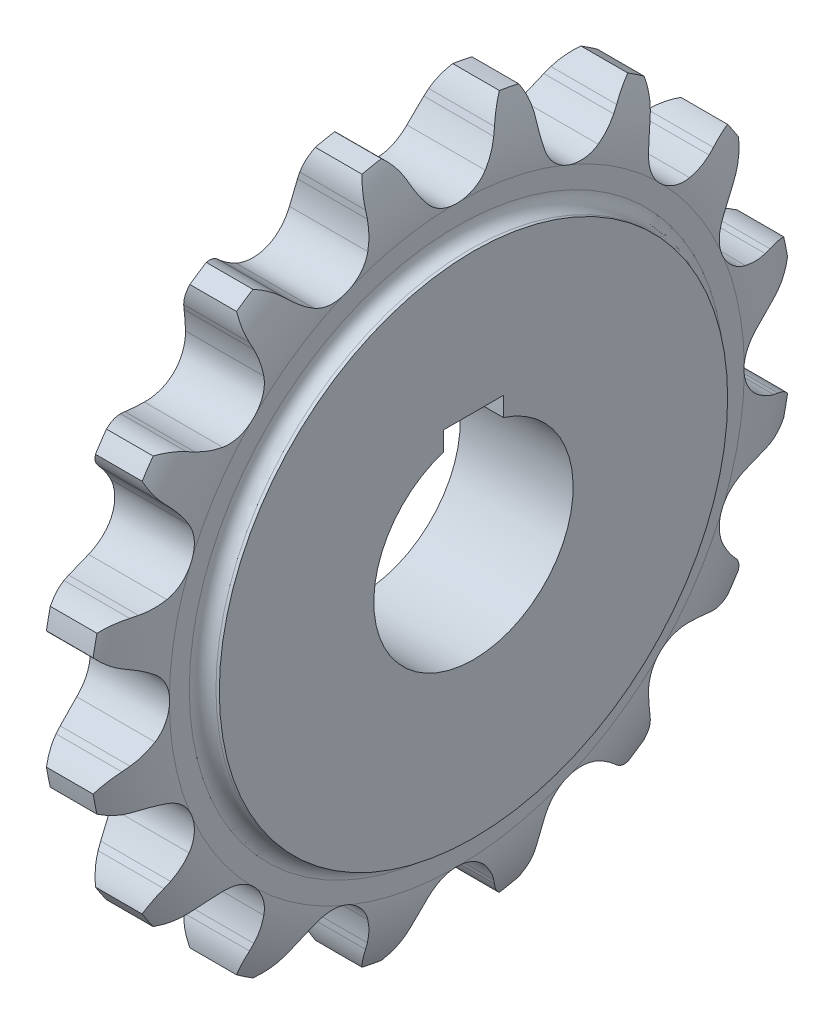
SolidWorks part; units mm, degrees
material "AISI 1020"
ref_plane "Front" through (0, 0, 0) normal (0, 0, 1) x (1, 0, 0)
ref_plane "Top" through (0, 0, 0) normal (0, 1, 0) x (1, 0, 0)
ref_plane "Right" through (0, 0, 0) normal (1, 0, 0) x (0, 0, -1)
sketch "Sketch1" plane through (0, 0, 0) normal (0, 0, 1) x (1, 0, 0)
  line L0 (-4, 0) -> (4, 0) construction
  line L1 (-16.9955, 0) -> (-16.9955, 76.5)
  line L2 (-16.9955, 76.5) -> (-15.9923, 76.5)
  line L3 (-11.9795, 80.5128) -> (-11.9795, 86.5321)
  line L4 (-7.0265, 106) -> (7.0265, 106)
  line L5 (11.9795, 86.5321) -> (11.9795, 80.5128)
  line L6 (15.9923, 76.5) -> (16.9955, 76.5)
  line L7 (16.9955, 76.5) -> (16.9955, 0)
  line L8 (16.9955, 0) -> (-16.9955, 0)
  line L9 (0, 0) -> (0, 106) construction
  line L10 (-10.5264, 97.6471) -> (10.5264, 97.6471) construction
  line L11 (-10.5264, -97.6471) -> (10.5264, -97.6471) construction
  line L13 (-11.9795, 86.5321) -> (3.7984, 86.5321) construction
  line L14 (-11.9795, -86.5321) -> (3.7984, -86.5321) construction
  arc A0 (-7.0265, 106) -> (-11.9795, 86.5321) centre (26.1146, 87.2043) ccw
  arc A1 (7.0265, 106) -> (11.9795, 86.5321) centre (-26.1146, 87.2043) cw
  arc A2 (11.9795, 80.5128) -> (15.9923, 76.5) centre (15.9923, 80.5128) ccw
  arc A3 (-15.9923, 76.5) -> (-11.9795, 80.5128) centre (-15.9923, 80.5128) ccw
  point P30 (11.9795, 76.5)
  point P33 (-11.9795, 76.5)
  point P34 (24, 26.331)
  point P36 (46.23, 26.331)
  point P37 (24, 21.8279)
  point P38 (60.2, 21.8279)
  point P39 (24, 17.1531)
  point P40 (49.22, 17.1531)
  point P41 (24, 13.3224)
  point P42 (69.44, 13.3224)
  point P43 (24, 30.8002)
  point P44 (40, 30.8002)
  point P45 (24, 35.1098)
  point P46 (62.1, 35.1098)
  dimension "D1" = 10.0321
  dimension "rx" = 38.1
  dimension "D3" = 4.0128
  dimension "d" = 195.2942
  dimension "p" = 38.1
  dimension "z" = 16
  dimension "da" = 212
  dimension "df" = 173.0642
  dimension "dr" = 22.23
  dimension "dg" = 153
  dimension "h" = 36.2
  dimension "bf1" = 23.959
  dimension "b1" = 25.22
  dimension "ba" = 4.953
  dimension "D2" = 5.016
  dimension "pt" = 45.44
revolve "Revolve" add sketch "Sketch1" angle 360 about L0
ref_axis "Axis1" through (-8.5448, 0, 0) along (1, 0, 0)
sketch "Sketch2" plane through (0, 0, 0) normal (1, 0, 0) x (0, 0, -1)
  line L0 (0, 0) -> (0, 106) construction
  line L1 (0, 0) -> (-20.6796, 103.9632) construction
  line L2 (0, 0) -> (-40.5644, 97.9312) construction
  line L3 (8.7508, 90.6239) -> (32.0778, 71.9019) construction
  line L4 (12.5758, 96.8658) -> (-13.8695, 108.7785) construction
  line L5 (0, 0) -> (20.6796, 103.9632) construction
  line L6 (12.5758, 96.8658) -> (13.417, 98.7332)
  line L7 (-12.5758, 96.8658) -> (-13.417, 98.7332)
  circle A0 centre (0, 0) radius 106 construction
  arc A1 (8.7508, 90.6239) -> (-8.7508, 90.6239) centre (0, 97.6471) cw
  arc A2 (8.7508, 90.6239) -> (12.5758, 96.8658) centre (-13.8695, 108.7785) ccw
  arc A3 (17.7622, 104.5012) -> (13.417, 98.7332) centre (28.3437, 92.0092) ccw
  arc A4 (-8.7508, 90.6239) -> (-12.5758, 96.8658) centre (13.8695, 108.7785) cw
  arc A5 (-17.7622, 104.5012) -> (-13.417, 98.7332) centre (-28.3437, 92.0092) cw
  arc A7 (17.7622, 104.5012) -> (-17.7622, 104.5012) centre (0, 0) ccw
  dimension "r1" = 11.2206
  dimension "r3" = 16.3713
  dimension "D1" = 22.5
  dimension "D2" = 11.25
  dimension "av2" = 51.25
  dimension "M" = 13.8695
  dimension "T" = 11.1314
  dimension "beta" = 14.5
  dimension "yv2" = 13
  dimension "bc" = 2.0481
extrude "ExtrudeCutOne" cut sketch "Sketch2" against normal mid plane 33.9911
pattern_circular "PatternOne" count 16 over 360 about axis through (-4, 0, 0) along (1, 0, 0) of "ExtrudeCutOne"
sketch "Cut-ExtrudeA" plane through (0, 0, 0) normal (1, 0, 0) x (0, 0, -1)
  circle A0 centre (0, 0) radius 30
sketch "SketchKey" plane through (0, 0, 0) normal (1, 0, 0) x (0, 0, -1)
  line L1 (-9, 15) -> (9, 15)
  line L2 (-9, 15) -> (-9, 34.4)
  line L3 (-9, 34.4) -> (9, 34.4)
  line L4 (9, 15) -> (9, 34.4)
extrude "Cut-ExtrudeB" cut sketch "SketchKey" against normal through all and the other way through all
sketch "草图3" plane through (16.9955, 0, 0) normal (1, 0, 0) x (0, 0, -1)
  circle A0 centre (0, 0) radius 30
  dimension "D1" = 60
extrude "切除-拉伸3" cut sketch "草图3" against normal up to next
